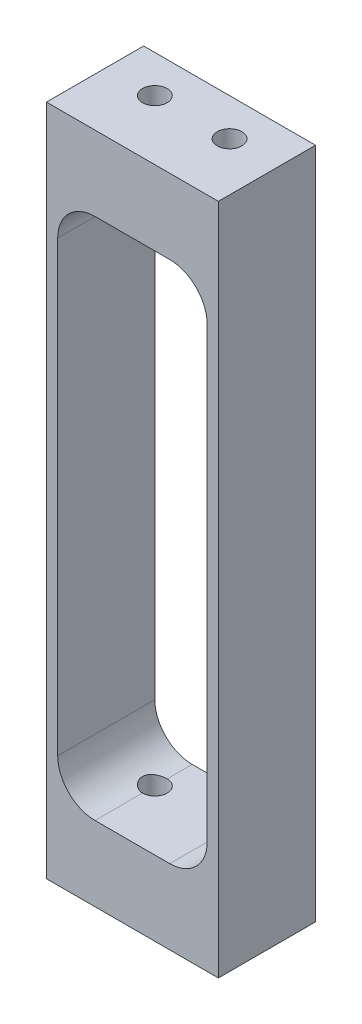
SolidWorks part; units mm, degrees
ref_plane "Front Plane" through (0, 0, 0) normal (0, 0, 1) x (1, 0, 0)
ref_plane "Top Plane" through (0, 0, 0) normal (0, 1, 0) x (1, 0, 0)
ref_plane "Right Plane" through (0, 0, 0) normal (1, 0, 0) x (0, 0, -1)
sketch "Sketch1" plane through (0, 0, 0) normal (0, 0, 1) x (1, 0, 0)
  line L1 (-11.5, -45) -> (11.5, -45)
  line L2 (-11.5, -45) -> (-11.5, 45)
  line L3 (-11.5, 45) -> (11.5, 45)
  line L4 (11.5, -45) -> (11.5, 45)
  line L5 (-11.5, -45) -> (11.5, 45) construction
  line L6 (-11.5, 45) -> (11.5, -45) construction
  point P0 (0, 0)
  dimension "D1" = 90
  dimension "D2" = 23
extrude "Boss-Extrude1" add sketch "Sketch1" along normal blind 13
sketch "Sketch2" plane through (0, 0, 13) normal (0, 0, 1) x (1, 0, 0)
  line L1 (-10, -35) -> (10, -35)
  line L2 (-10, -35) -> (-10, 35)
  line L3 (-10, 35) -> (10, 35)
  line L4 (10, -35) -> (10, 35)
  line L5 (-10, -35) -> (10, 35) construction
  line L6 (-10, 35) -> (10, -35) construction
  point P0 (0, 0)
  dimension "D1" = 20
  dimension "D2" = 70
extrude "Cut-Extrude1" cut sketch "Sketch2" against normal blind 23
fillet "Fillet1" radius 5 4 edges at (-10, 35, 6.5) (10, 35, 6.5) (10, -35, 6.5) (-10, -35, 6.5)
hole_wizard "M4x0.7 Tapped Hole1" positions "Sketch3" profile "Sketch4" tap size "M4x0.7" standard "ANSI Metric" end condition through all
sketch "Sketch3" plane through (0, -45, 0) normal (0, -1, 0) x (-1, 0, 0)
  line L0 (-5, -5) -> (5, -5)
  line L2 (11.5, -13) -> (-11.5, -13) construction
  point P1 (-5, -5)
  point P2 (5, -5)
  point P7 (0, -5)
  dimension "D1" = 10
  dimension "D2" = 8
sketch "Sketch4" plane through (5, -45, 5) normal (1, 0, 0) x (0, 0, -1)
  line L0 (0, 0) -> (0, 90)
  line L1 (0, 90) -> (1.65, 90)
  line L2 (1.65, 90) -> (1.65, 0)
  line L5 (1.65, 0) -> (0, 0)
  line L11 (0, -6.35) -> (0, 107.95) construction
  dimension "Thru Tap Drill Dia." = 3.3
  dimension "Thru Tap Drill Depth" = 90
cosmetic thread "Hole Thread1" parameters "D2"=4
cosmetic thread "Hole Thread2" parameters "D2"=4
